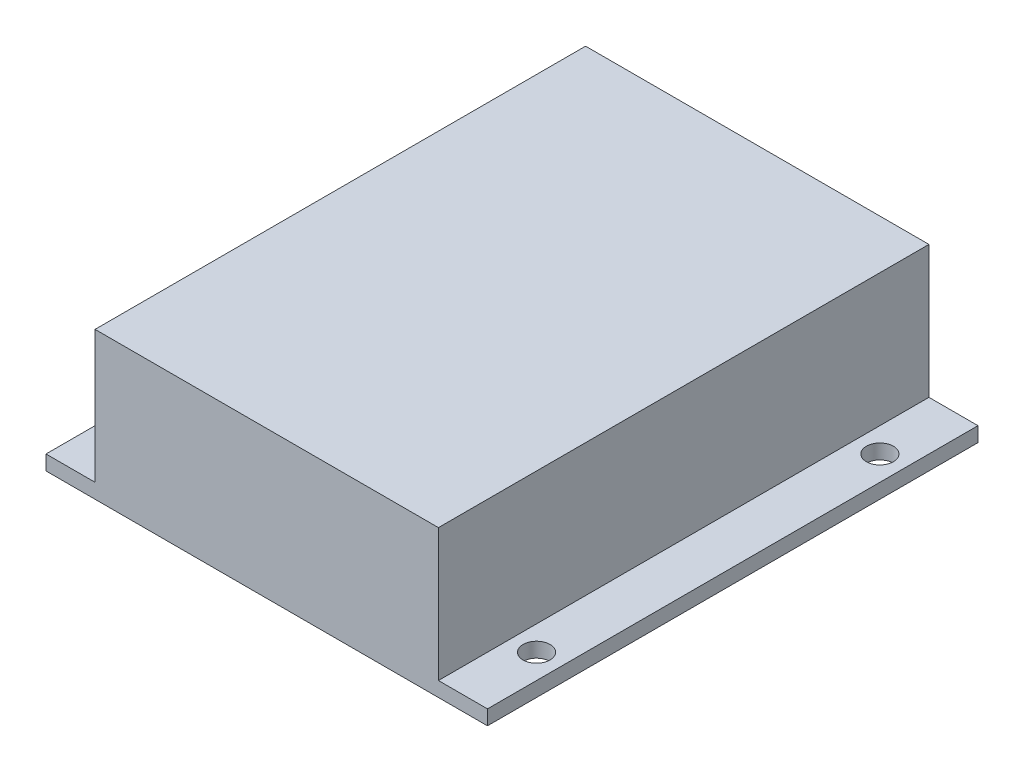
SolidWorks part; units mm, degrees
note: The reader was unsure of these and kept them because the rebuilt part matched: shared geometry of "Sketch1<4>".
material "1060 Alloy"
ref_plane "Front Plane" through (0, 0, 0) normal (0, 0, 1) x (1, 0, 0)
ref_plane "Top Plane" through (0, 0, 0) normal (0, 1, 0) x (1, 0, 0)
ref_plane "Right Plane" through (0, 0, 0) normal (1, 0, 0) x (0, 0, -1)
sketch "Sketch1" plane through (0, 0, 0) normal (0, 1, 0) x (1, 0, 0)
  line L0 (-40, -35) -> (-40, 35) construction
  line L1 (45, 50) -> (-45, 50)
  line L2 (45, 50) -> (45, -50)
  line L3 (45, -50) -> (-45, -50)
  line L4 (-45, 50) -> (-45, -50)
  line L5 (45, 50) -> (-45, -50) construction
  line L6 (45, -50) -> (-45, 50) construction
  line L7 (35, 50) -> (-35, 50)
  line L8 (35, 50) -> (35, -50)
  line L9 (35, -50) -> (-35, -50)
  line L10 (-35, 50) -> (-35, -50)
  line L11 (35, 50) -> (-35, -50) construction
  line L12 (35, -50) -> (-35, 50) construction
  line L13 (45, -35) -> (-45, -35) construction
  line L14 (45, -35) -> (45, 35)
  line L15 (45, 35) -> (-45, 35) construction
  line L16 (-45, -35) -> (-45, 35)
  line L17 (45, -35) -> (-45, 35) construction
  line L18 (45, 35) -> (-45, -35) construction
  line L19 (-40, 35) -> (40, 35) construction
  line L20 (-40, 35) -> (-40, -35) construction
  circle A0 centre (-40, 35) radius 2.5 construction
  circle A1 centre (40, 35) radius 2.5 construction
  circle A2 centre (40, -35) radius 2.5 construction
  circle A3 centre (-40, -35) radius 2.5 construction
  point P0 (0, 0)
  point P6 (0, 0)
  point P11 (0, 0)
  dimension "D6" = 5
  dimension "D1" = 90
  dimension "D2" = 100
  dimension "D3" = 70
  dimension "D4" = 70
  dimension "D5" = 5
  dimension "D9" = 80
  dimension "D10" = 70
  dimension "D7" = 2
  dimension "D8" = 2
extrude "Boss-Extrude1" add sketch "Sketch1" along normal blind 30 contours L1 L10 L3 L8
extrude "Boss-Extrude3" add sketch "Sketch1<4>" along normal blind 3 contours L10 L1 L4 L3 | L1 L8 L3 L2
sketch "Sketch1<4>" plane through (0, 0, 0) normal (0, 1, 0) x (1, 0, 0) same geometry as "Sketch1"
hole_wizard "M5 Clearance Slot1" positions "Sketch3" profile "Sketch5" size "M5" standard "ANSI Metric" slot yes
sketch "Sketch3" plane through (0, 0, 0) normal (0, -1, 0) x (-1, 0, 0)
  point P0 (40, 35)
  point P3 (40, -35)
  point P6 (-40, 35)
  point P9 (-40, -35)
sketch "Sketch5" plane through (-40, 0, -35) normal (1, 0, 0) x (0, 0, -1)
  line L0 (0, 0) -> (0, 23.9024)
  line L1 (0, 23.9024) -> (2.75, 22.25)
  line L2 (2.75, 22.25) -> (2.75, 0)
  line L5 (2.75, 0) -> (0, 0)
  line L10 (0, 23.9024) -> (-2.75, 22.25) construction
  line L11 (0, -6.35) -> (0, 107.95) construction
  dimension "Hole Dia." = 5.5
  dimension "Hole Depth" = 22.25
  dimension "Drill Angle" = 118
